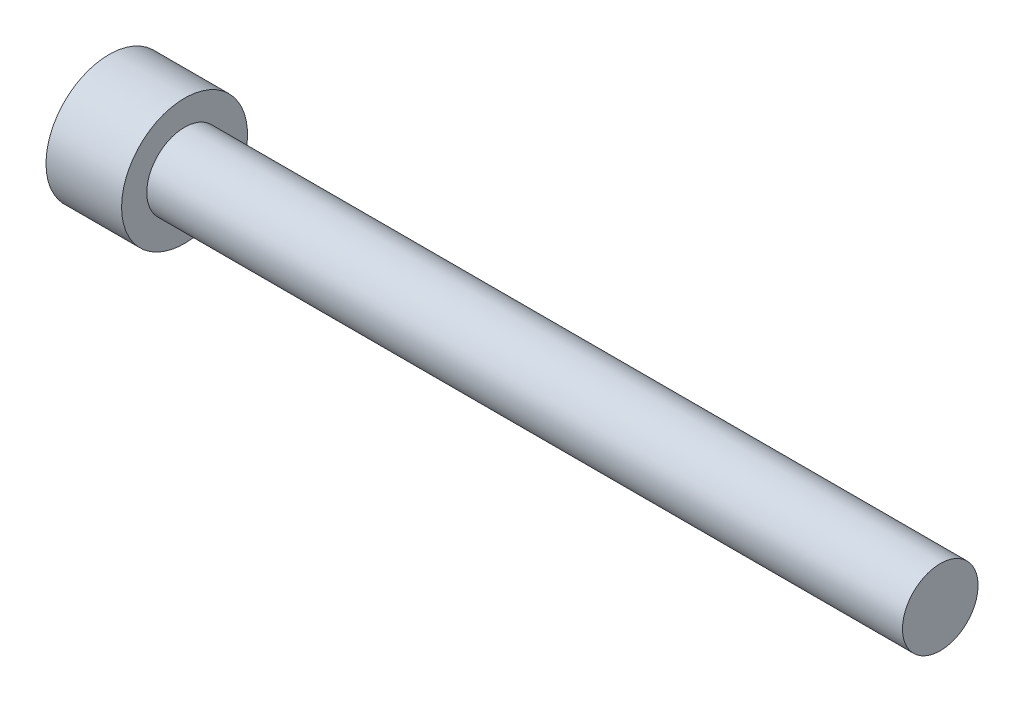
SolidWorks part; units mm, degrees
ref_plane "Front Plane" through (0, 0, 0) normal (0, 0, 1) x (1, 0, 0)
ref_plane "Top Plane" through (0, 0, 0) normal (0, 1, 0) x (1, 0, 0)
ref_plane "Right Plane" through (0, 0, 0) normal (1, 0, 0) x (0, 0, -1)
sketch "Screw Sketch" plane through (0, 0, 0) normal (0, 0, 1) x (1, 0, 0)
  line L0 (-1000, 0) -> (1000, 0) construction
  line L1 (-6, 0) -> (-6, 5)
  line L2 (-6, 5) -> (0, 5)
  line L3 (0, 5) -> (0, 3)
  line L4 (0, 3) -> (60, 3)
  line L5 (60, 3) -> (60, 0)
  line L6 (60, 0) -> (-6, 0)
revolve "Screw" add sketch "Screw Sketch" angle 360 about L0
ref_axis "Engine Axis" through (63.3, 0, 0) along (-1, 0, 0)
ref_plane "Head Top" through (-6, 0, 0) normal (1, 0, 0) x (0, 0, -1)
sketch "Socket Sketch" plane through (-6, 0, 0) normal (1, 0, 0) x (0, 0, -1)
  line L0 (2.8868, 0) -> (1.4434, 2.5)
  line L1 (1.4434, 2.5) -> (-1.4434, 2.5)
  line L2 (-1.4434, 2.5) -> (-2.8868, 0)
  line L3 (-2.8868, 0) -> (-1.4434, -2.5)
  line L4 (-1.4434, -2.5) -> (1.4434, -2.5)
  line L5 (1.4434, -2.5) -> (2.8868, 0)
extrude "Socket" cut sketch "Socket Sketch" along normal blind 3
